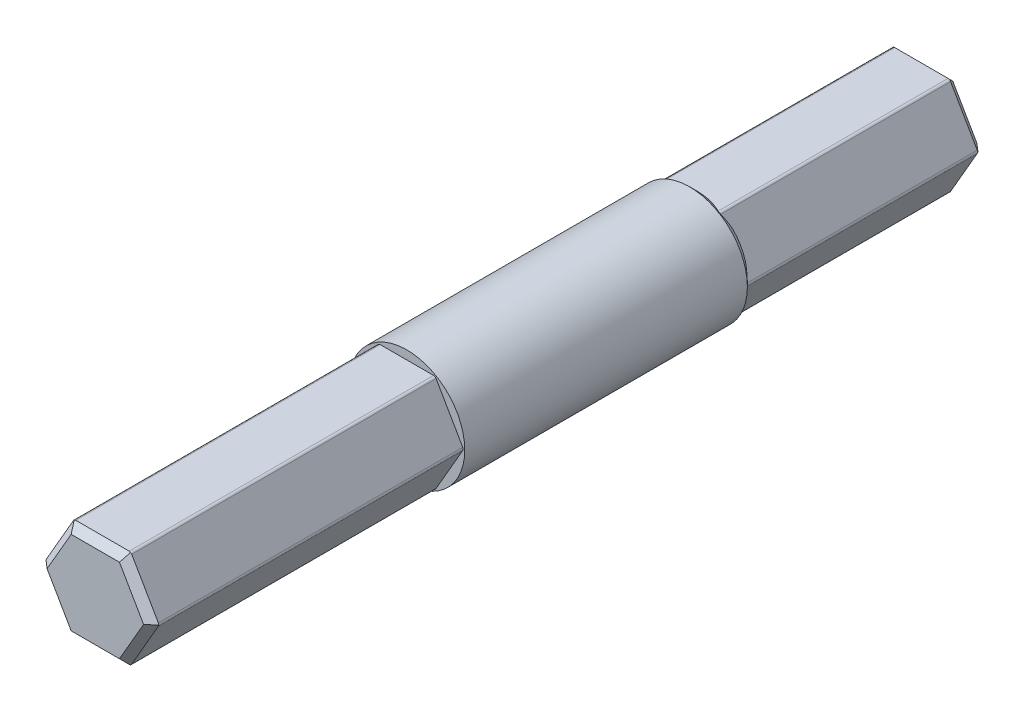
SolidWorks part; units mm, degrees
material "PETG"
ref_plane "Front Plane" through (0, 0, 0) normal (0, 0, 1) x (1, 0, 0)
ref_plane "Top Plane" through (0, 0, 0) normal (0, 1, 0) x (1, 0, 0)
ref_plane "Right Plane" through (0, 0, 0) normal (1, 0, 0) x (0, 0, -1)
sketch "Sketch1" plane through (0, 0, 0) normal (0, 0, 1) x (1, 0, 0)
  circle A0 centre (0, 0) radius 3.99
  dimension "Shaft Dia" = 7.98
extrude "Boss-Extrude1" add sketch "Sketch1" along normal blind 20
sketch "Sketch2" plane through (0, 0, 20) normal (0, 0, 1) x (1, 0, 0)
  line L1 (4, 0) -> (2, 3.4641) construction
  line L2 (2, 3.4641) -> (-2, 3.4641) construction
  line L3 (-2, 3.4641) -> (-4, 0) construction
  line L4 (-4, 0) -> (-2, -3.4641) construction
  line L5 (-2, -3.4641) -> (2, -3.4641) construction
  line L6 (2, -3.4641) -> (4, 0) construction
  line L7 (3.9076, 0) -> (1.9538, 3.3841)
  line L8 (1.9538, 3.3841) -> (-1.9538, 3.3841)
  line L9 (-1.9538, 3.3841) -> (-3.9076, 0)
  line L10 (-3.9076, 0) -> (-1.9538, -3.3841)
  line L11 (-1.9538, -3.3841) -> (1.9538, -3.3841)
  line L12 (1.9538, -3.3841) -> (3.9076, 0)
  circle A0 centre (0, 0) radius 3.4641 construction
  circle A1 centre (0, 0) radius 3.3841 construction
  dimension "Hex Circumscribed Nominal Dia" = 8
  dimension "Hex Flat To Flat Offset" = 0.08
extrude "Boss-Extrude2" add sketch "Sketch2" along normal blind 21.5
sketch "Sketch3" plane through (0, 0, 0) normal (0, 0, -1) x (-1, 0, 0)
  line L0 (-1.9538, 3.3841) -> (1.9538, 3.3841) construction
  line L13 (3.9076, 0) -> (1.9538, 3.3841)
  line L14 (1.9538, 3.3841) -> (-1.9538, 3.3841)
  line L15 (-1.9538, 3.3841) -> (-3.9076, 0)
  line L16 (-3.9076, 0) -> (-1.9538, -3.3841)
  line L17 (-1.9538, -3.3841) -> (1.9538, -3.3841)
  line L18 (1.9538, -3.3841) -> (3.9076, 0)
  circle A1 centre (0, 0) radius 3.3841 construction
extrude "Boss-Extrude3" add sketch "Sketch3" along normal blind 16
chamfer "Chamfer1" distance 0.5 angle 45 12 edges at (0, -3.3841, 41.5) (-2.9307, -1.6921, 41.5) (-2.9307, 1.6921, 41.5) (0, 3.3841, 41.5) (2.9307, 1.6921, 41.5) (2.9307, -1.6921, 41.5) (0, -3.3841, -16) (2.9307, -1.6921, -16) (2.9307, 1.6921, -16) (0, 3.3841, -16) (-2.9307, 1.6921, -16) (-2.9307, -1.6921, -16)
fillet "Fillet1" radius 0.2 12 edges at (-1.9538, 3.3841, -7.75) (-3.9076, 0, -7.75) (1.9538, 3.3841, -7.75) (3.9076, 0, -7.75) (1.9538, -3.3841, -7.75) (-1.9538, -3.3841, -7.75) (1.9538, -3.3841, 30.5) (-1.9538, -3.3841, 30.5) (-3.9076, 0, 30.5) (-1.9538, 3.3841, 30.5) (3.9076, 0, 30.5) (1.9538, 3.3841, 30.5)
chamfer "Chamfer2" distance 0.5 angle 45 1 edges at (3.99, 0, 0)
equation "\"tol_dia_id_intfc\" = 0.0200mm ' For hole diameters - Interference fit"
equation "\"tol_dia_id_slip\"  = 0.0300mm ' For hole diameters - Slip fit"
equation "\"tol_dia_id_clear\" = 0.0500mm ' For hole diameters - Clearance fit"
equation "\"tol_dia_od_intfc\" = 0.0200mm ' For shaft diameters - Interference fit"
equation "\"tol_dia_od_slip\"  = 0.0300mm ' For shaft diameters - Slip fit"
equation "\"tol_dia_od_clear\" = 0.0500mm ' For shaft diameters - Clearance fit"
equation "\"tol_general_intfc\"= 0.0030mm ' For general parts (Horiz) - Interference fit"
equation "\"tol_general_slip\" = 0.0050mm ' For general parts (Horiz) - Slip fit"
equation "\"tol_general_clear\"= 0.0100mm ' For general parts (Horiz) - Clearance fit"
equation "\"tol_layer_intfc\"  = 0.0030mm ' For all parts (Vert) - Interference fit"
equation "\"tol_layer_slip\"   = 0.0050mm ' For all parts (Vert) - Slip fit"
equation "\"tol_layer_clear\"  = 0.0100mm ' For all parts (Vert) - Clearance fit"
equation "\"tol_corner_rad\"   = 0.100mm ' For corners that fit into other parts"
equation "\"Shaft Dia@Sketch1\" = \"nominal_dia\" - \"tol_dia_od_intfc\""
equation "\"nominal_dia\"= 8.00mm"
equation "\"Hex Circumscribed Nominal Dia@Sketch2\" = \"nominal_dia\""
equation "\"Hex Flat To Flat Offset@Sketch2\"=\"tol_general_slip\"+0.0750"
equation "\"D1@Fillet1\"=\"tol_corner_rad\"*2"
equation "\"D1@Boss-Extrude2\"=21.5"
